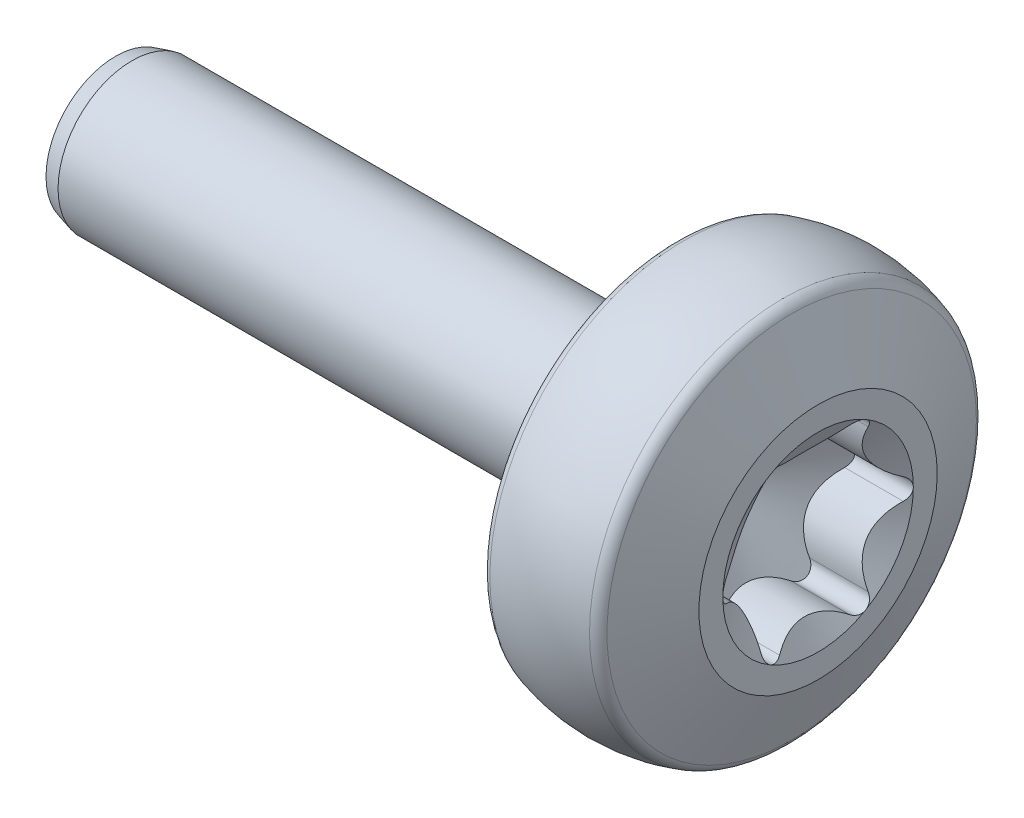
SolidWorks part; units mm, degrees
material "Alloy Steel"
ref_plane "Front Plane" through (0, 0, 0) normal (0, 0, 1) x (1, 0, 0)
ref_plane "Top Plane" through (0, 0, 0) normal (0, 1, 0) x (1, 0, 0)
ref_plane "Right Plane" through (0, 0, 0) normal (1, 0, 0) x (0, 0, -1)
sketch "Sketch1" plane through (0, 0, 0) normal (0, 0, 1) x (1, 0, 0)
  line L0 (-5.9944, 0) -> (5.9944, 0) construction
  line L1 (-5.9944, 1.8669) -> (-5.9944, -1.8669) construction
  line L2 (3.5306, 3.429) -> (3.5306, -3.429) construction
  line L3 (5.9944, 1.6256) -> (5.9944, -1.6256) construction
  line L4 (-6.4272, 2.0116) -> (-5.8423, 0.9986) construction
  line L5 (-5.8423, 0.9986) -> (-7.0121, 0.9986) construction
  line L6 (-7.0121, 0.9986) -> (-6.4272, 2.0116) construction
  line L7 (-7.0121, 0.9986) -> (-7.0956, 0.8539) construction
  line L8 (-7.0956, 0.8539) -> (-5.7588, 0.8539) construction
  line L9 (-5.7588, 0.8539) -> (-5.8423, 0.9986) construction
  line L10 (-6.5108, 1.8669) -> (-6.3437, 1.8669) construction
  line L11 (-6.4272, 2.0116) -> (-6.4272, 1.8669) construction
  line L12 (-6.4272, 0.9986) -> (-6.4272, 0.8539) construction
  point P11 (3.5306, 0)
  point P12 (-5.9944, 1.262)
  dimension "Screw Size Decimal Equivalent" = 3.7338
  dimension "Torx Diameter" = 3.2512
  dimension "Head Diameter" = 6.858
  dimension "Head Height" = 2.4638
  dimension "Length" = 9.525
  dimension "Thread ID" = 2.524
  dimension "Approximate Thread Pitch" = 1.3368
  dimension "D1" = 0.1671
sketch "Sketch2" plane through (0, 0, 0) normal (0, 0, 1) x (1, 0, 0)
  line L0 (-5.9944, 0) -> (5.9944, 0)
  line L1 (5.9944, 0) -> (5.9944, 2.0336)
  line L2 (-5.9944, 0) -> (-5.9944, 1.262)
  line L3 (-5.9944, 1.262) -> (3.4544, 1.262)
  line L6 (3.4544, 1.262) -> (3.4544, 1.9272)
  line L9 (-5.9944, 0) -> (-17.9832, 0) construction
  line L10 (3.4544, 1.9272) -> (3.4544, 2.5924) construction
  line L11 (5.9944, 1.6256) -> (5.9944, 2.0336) construction
  line L12 (3.4544, 2.5924) -> (3.4544, 3.2576) construction
  line L14 (5.9944, 3.2576) -> (3.5306, 3.2576) construction
  line L15 (3.5306, 3.2576) -> (3.5306, 1.262) construction
  line L17 (3.5306, 3.2576) -> (3.5306, 2.0034)
  line L18 (3.5306, 3.429) -> (3.5306, -3.429) construction
  line L19 (5.9944, 1.6256) -> (5.9944, -1.6256) construction
  line L20 (5.9944, 2.0336) -> (5.9944, 2.4416) construction
  line L21 (5.9944, 2.4416) -> (5.9944, 2.8496) construction
  line L22 (5.9944, 2.8496) -> (5.9944, 3.2576) construction
  line L23 (5.9944, 2.0336) -> (5.5016, 3.2576)
  arc A6 (5.5016, 3.2576) -> (3.5306, 3.2576) centre (4.5161, 0.5108) ccw
  arc A7 (3.5306, 2.0034) -> (3.4925, 1.9653) centre (3.4925, 2.0034) cw
  arc A8 (3.4925, 1.9653) -> (3.4544, 1.9272) centre (3.4925, 1.9272) ccw
  point P14 (4.5161, 3.429)
  dimension "D1" = 6.5151
  dimension "D2" = 0.0762
  dimension "D3" = 1.971
revolve "Revolve1" add sketch "Sketch2" angle 360 about L9
sketch "Sketch12" plane through (0, 0, 0) normal (0, 0, 1) x (1, 0, 0)
  line L0 (5.9944, 1.6256) -> (4.9935, 1.6256)
  line L1 (4.9935, 1.6256) -> (4.0549, 0)
  line L2 (-5.9944, 0) -> (5.9944, 0) construction
  line L3 (4.0549, 0) -> (5.9944, 0)
  line L4 (5.9944, 0) -> (5.9944, 1.6256)
  dimension "D1" = 60
  dimension "D2" = 1.0009
revolve "Cut-Revolve3" cut sketch "Sketch12" angle 360 about L0
sketch "Sketch3" plane through (5.9944, 0, 0) normal (1, 0, 0) x (0, 0, -1)
  line L0 (1.2192, 0) -> (1.4224, 0) construction
  line L1 (1.4224, 0) -> (1.6256, 0) construction
  line L2 (-0.8128, 1.4078) -> (0, 0) construction
  line L3 (0, 0) -> (0.8128, 1.4078) construction
  line L4 (0.8128, 1.4078) -> (-0.8128, 1.4078) construction
  circle A0 centre (0, 0) radius 1.6256 construction
  circle A1 centre (0, 0) radius 1.4224 construction
  circle A2 centre (0, 0) radius 1.2192 construction
  circle A51 centre (0, 0) radius 2.0336
  arc A54 (1.5122, -0.1823) -> (1.6256, 0) centre (1.4224, 0) ccw
  arc A55 (-0.5983, 1.4008) -> (0.5983, 1.4008) centre (0, 2.2957) ccw
  arc A56 (-0.5983, 1.4008) -> (-0.8128, 1.4078) centre (-0.7112, 1.2318) ccw
  arc A57 (1.5122, -0.1823) -> (0.914, -1.2185) centre (1.9881, -1.1478) ccw
  arc A58 (0.8128, 1.4078) -> (0.5983, 1.4008) centre (0.7112, 1.2318) ccw
  arc A59 (0.914, 1.2185) -> (0.8128, 1.4078) centre (0.7112, 1.2318) ccw
  arc A60 (0.8128, -1.4078) -> (0.914, -1.2185) centre (0.7112, -1.2318) ccw
  arc A61 (0.914, 1.2185) -> (1.5122, 0.1823) centre (1.9881, 1.1478) ccw
  arc A62 (1.6256, 0) -> (1.5122, 0.1823) centre (1.4224, 0) ccw
  arc A63 (0.5983, -1.4008) -> (0.8128, -1.4078) centre (0.7112, -1.2318) ccw
  arc A76 (0.5983, -1.4008) -> (-0.5983, -1.4008) centre (0, -2.2957) ccw
  arc A77 (-0.8128, -1.4078) -> (-0.5983, -1.4008) centre (-0.7112, -1.2318) ccw
  arc A78 (-0.914, -1.2185) -> (-0.8128, -1.4078) centre (-0.7112, -1.2318) ccw
  arc A79 (-0.914, -1.2185) -> (-1.5122, -0.1823) centre (-1.9881, -1.1478) ccw
  arc A80 (-1.6256, 0) -> (-1.5122, -0.1823) centre (-1.4224, 0) ccw
  arc A81 (-1.5122, 0.1823) -> (-1.6256, 0) centre (-1.4224, 0) ccw
  arc A82 (-1.5122, 0.1823) -> (-0.914, 1.2185) centre (-1.9881, 1.1478) ccw
  arc A83 (-0.8128, 1.4078) -> (-0.914, 1.2185) centre (-0.7112, 1.2318) ccw
  point P20 (0, 1.2192)
  point P58 (0, 0)
  point P72 (0, 0)
  dimension "D1" = 2.4384
  dimension "D2" = 6
extrude "Boss-Extrude1" add sketch "Sketch3" against normal up to surface (1.0601 mm away)
sketch "Sketch4" plane through (5.9944, 0, 0) normal (1, 0, 0) x (0, 0, -1)
  circle A0 centre (0, 0) radius 1.6256
extrude "Cut-Extrude2" cut sketch "Sketch4" against normal through all draft 60
fillet "Fillet1" radius 0.2464 2 edges at (3.5306, 0, -3.2576) (5.5016, 0, -3.2576)
chamfer "Chamfer1" distance 0.2807 angle 15 1 edges at (-5.9944, 0, -1.262) first distance on face at (-5.9944, 0, -1.262)
split "Split1" [suppressed] bodies to split 106
sketch "Sketch9" [suppressed] plane through (0, 0, 0) normal (0, 0, 1) x (1, 0, 0)
  line L0 (-5.9944, 1.8669) -> (-5.9944, 0)
  line L1 (-5.9944, 0) -> (3.4544, 0)
  line L2 (-5.9944, 0) -> (5.9944, 0) construction
  line L3 (3.4544, 0) -> (3.4544, 1.8669)
  line L5 (3.4544, 1.8669) -> (-5.9944, 1.8669)
revolve "Revolve2" [suppressed] add sketch "Sketch9" angle 360 about L0
sketch "Sketch5" [suppressed] plane through (-5.9944, 0, 0) normal (-1, 0, 0) x (0, 0, 1)
  circle A0 centre (0, 0) radius 1.262
curve "Helix/Spiral1" [suppressed] pitch 1.3368 height 12.1987 turns 9.125
sketch "Sketch7" [suppressed] plane through (0, 0, 0) normal (0, 0, 1) x (1, 0, 0)
  line L0 (-5.9944, 1.262) -> (-6.226, 1.324) construction
  line L1 (-6.226, 1.324) -> (-6.3715, 1.8669) construction
  line L2 (-6.5108, 1.8669) -> (-6.3437, 1.8669) construction
  line L3 (-6.3715, 1.8669) -> (-6.4829, 1.8669) construction
  line L4 (-6.4829, 1.8669) -> (-6.6284, 1.324)
  line L5 (-6.6284, 1.324) -> (-6.86, 1.262)
  line L6 (-7.0121, 0.9986) -> (-6.4272, 2.0116) construction
  line L7 (-6.86, 1.262) -> (-6.86, 0.9986) construction
  line L8 (-5.8423, 0.9986) -> (-7.0121, 0.9986) construction
  line L9 (-6.86, 0.9986) -> (-5.9944, 0.9986) construction
  line L10 (-5.9944, 0.9986) -> (-5.9944, 1.262) construction
  line L11 (-6.4272, 0.9986) -> (-6.4272, 0.8539) construction
  line L12 (-7.0956, 0.8539) -> (-7.1792, 0.9986) construction
  line L13 (-7.1792, 0.9986) -> (-7.764, 2.0116) construction
  line L14 (-6.4272, 2.0116) -> (-5.8423, 0.9986) construction
  line L15 (-5.7588, 0.8539) -> (-5.8423, 0.9986) construction
  line L16 (-7.3312, 1.262) -> (-6.86, 1.262)
  line L19 (-7.3312, 1.262) -> (-7.5629, 1.324)
  line L20 (-7.5629, 1.324) -> (-7.7083, 1.8669)
  line L22 (-7.7083, 1.8669) -> (-7.7083, 2.0116)
  line L23 (-7.7083, 2.0116) -> (-6.4829, 2.0116)
  line L24 (-6.4829, 2.0116) -> (-6.4829, 1.8669)
  point P33 (-3.0294, -1.8669)
  dimension "D3" = 0.1114
  dimension "D1" = 15
  dimension "D2" = 15
  dimension "D4" = 3.3421
sweep "Cut-Sweep1" [suppressed] cut profiles "Sketch7" path "Helix/Spiral1"
combine bodies "Combine1" [suppressed] operation type add bodies to combine 107 113 119
sketch "Sketch13" [suppressed] plane through (3.4544, 0, 0) normal (-1, 0, 0) x (0, 0, 1)
  circle A0 centre (0, 0) radius 1.8415
  point P3 (0, 1.8415)
  dimension "D1" = 0.0254
extrude "Boss-Extrude2" [suppressed] add sketch "Sketch13" along normal through all draft 45
sketch "Sketch14" [suppressed] plane through (-5.9944, 0, 0) normal (-1, 0, 0) x (0, 0, 1)
  circle A2 centre (0, 0) radius 1.2366
  point P1 (0, 1.2366)
  dimension "D1" = 0.0254
extrude "Cut-Extrude3" [suppressed] cut sketch "Sketch14" against normal up to next draft 45 flip side to cut draft outward yes
equation "\"Thread ID@Sketch1\"=\"Screw Size Decimal Equivalent@Sketch1\"-(\"Approximate Thread Pitch@Sketch1\"*.905)"
equation "\"D1@Sketch3\"=\"Torx Diameter@Sketch1\"*.75"
equation "\"D4@Helix/Spiral1\"=\"Approximate Thread Pitch@Sketch1\""
equation "\"D3@Helix/Spiral1\"=\"Length@Sketch1\"+2*\"Approximate Thread Pitch@Sketch1\""
equation "\"D1@Sketch1\"=\"Approximate Thread Pitch@Sketch1\"/8"
equation "\"D3@Sketch7\"=\"Approximate Thread Pitch@Sketch1\"/12"
equation "\"D4@Sketch7\"=\"Approximate Thread Pitch@Sketch1\"*2.5"
equation "\"D2@Sketch12\"= \"Head Height@Sketch1\" * .40625"
equation "\"D1@Sketch2\"=\"Head Diameter@Sketch1\"*.95"
equation "\"D3@Sketch2\"=\"Head Height@Sketch1\"*.8"
equation "\"D1@Fillet1\"=\"Head Height@Sketch1\" * .1"
equation "\"D1@Chamfer1\"=\"approximate thread pitch@sketch1\"*.21"
